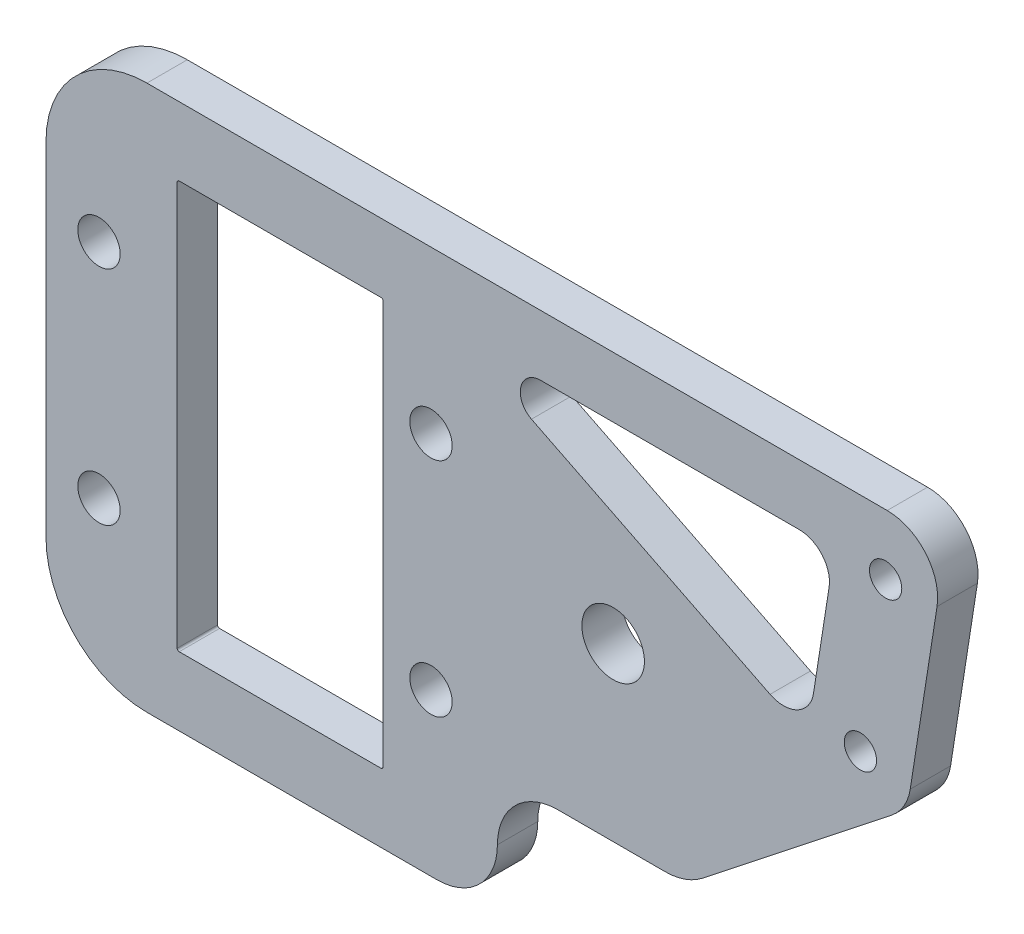
SolidWorks part; units mm, degrees
ref_plane "前视基准面" through (0, 0, 0) normal (0, 0, 1) x (1, 0, 0)
ref_plane "上视基准面" through (0, 0, 0) normal (0, 1, 0) x (1, 0, 0)
ref_plane "右视基准面" through (0, 0, 0) normal (1, 0, 0) x (0, 0, -1)
sketch "草图1" plane through (0, 0, 0) normal (0, 0, 1) x (1, 0, 0)
  line L0 (-10.2, 20.2) -> (10.2, 20.2)
  line L1 (-10, -20) -> (10, -20) construction
  line L2 (-10, -20) -> (-10, 20) construction
  line L3 (-10, 20) -> (10, 20) construction
  line L4 (10, -20) -> (10, 20) construction
  line L5 (-10, -20) -> (10, 20) construction
  line L6 (-10, 20) -> (10, -20) construction
  line L7 (10.2, -20.2) -> (10.2, 20.2)
  line L8 (-10.2, -20.2) -> (10.2, -20.2)
  line L9 (-10.2, -20.2) -> (-10.2, 20.2)
  line L10 (-13.2, 27) -> (60.1562, 27)
  line L11 (33, 25) -> (33, -25) construction
  line L12 (21.5311, -27) -> (-13.2, -27)
  line L13 (-23.2, -17) -> (-23.2, 17)
  line L15 (27.7237, -24.8519) -> (60.5963, 1.0741)
  line L16 (62.4401, 4.2281) -> (65.0963, 21.2281)
  circle A0 centre (33, 2) radius 3.1
  arc A1 (-13.2, -27) -> (-23.2, -17) centre (-13.2, -17) cw
  arc A2 (-13.2, 27) -> (-23.2, 17) centre (-13.2, 17) ccw
  circle A6 centre (33, 2) radius 12.5 construction
  circle A9 centre (60, 21) radius 1.6
  circle A10 centre (57.5, 5) radius 1.6
  arc A12 (60.5963, 1.0741) -> (62.4401, 4.2281) centre (57.5, 5) ccw
  arc A13 (21.5311, -27) -> (27.7237, -24.8519) centre (21.5311, -17) ccw
  arc A14 (65.0963, 21.2281) -> (60.1562, 27) centre (60.1562, 22) ccw
  point P0 (0, 0)
  point P32 (25, -27)
  dimension "D8" = 6.2
  dimension "D10" = 10
  dimension "D11" = 3.2
  dimension "D12" = 19
  dimension "D13" = 25
  dimension "D9" = 25
  dimension "D14" = 27
  dimension "D15" = 3.2
  dimension "D18" = 10
  dimension "D20" = 10
  dimension "D21" = 5
  dimension "D1" = 40
  dimension "D2" = 20
  dimension "D3" = 0.2
  dimension "D4" = 7
  dimension "D5" = 7
  dimension "D6" = 13
  dimension "D7" = 43
  dimension "D16" = 3
  dimension "D17" = 24.5
  dimension "D19" = 25
  dimension "D22" = 5
extrude "凸台-拉伸1" add sketch "草图1" along normal blind 4
fillet "圆角1" radius 0.2 4 edges at (10.2, -20.2, 2) (-10.2, -20.2, 2) (-10.2, 20.2, 2) (10.2, 20.2, 2)
sketch "草图2" plane through (0, 0, 4) normal (0, 0, 1) x (1, 0, 0)
  line L0 (14.95, 11) -> (14.95, -11) construction
  line L1 (9.95, 20.25) -> (9.95, -49979.75) construction
  line L2 (0, 0) -> (50000, 0) construction
  line L3 (10.2, -20) -> (10.2, 20) construction
  line L4 (0, 0.6321) -> (0, 50000.6321) construction
  line L5 (-17.95, 11) -> (-17.95, -11) construction
  circle A0 centre (14.95, 11) radius 2.1
  circle A4 centre (14.95, -11) radius 2.1
  circle A5 centre (-17.95, -11) radius 2.1
  circle A6 centre (-17.95, 11) radius 2.1
  dimension "D1" = 4.2
  dimension "D2" = 22
  dimension "D3" = 17.95
  dimension "D6" = 4.2
  dimension "D7" = 4.2
  dimension "D8" = 17.95
  dimension "D4" = 0.25
  dimension "D5" = 5
extrude "切除-拉伸1" cut sketch "草图2" against normal blind 4
sketch "草图3" plane through (0, 0, 4) normal (0, 0, 1) x (1, 0, 0)
  line L0 (25.798, 21) -> (51.4342, 21)
  line L1 (54.3982, 17.5369) -> (52.8522, 7.6426)
  line L2 (48.5495, 5.4209) -> (24.9056, 17.2102)
  line L3 (60.1562, 27) -> (-13.2, 27) construction
  line L4 (14.95, 11) -> (33, 2) construction
  line L5 (57.5, 5) -> (60, 21) construction
  line L6 (62.4401, 4.2281) -> (65.0963, 21.2281) construction
  arc A0 (54.3982, 17.5369) -> (51.4342, 21) centre (51.4342, 18) ccw
  arc A1 (24.9056, 17.2102) -> (25.798, 21) centre (25.798, 19) cw
  arc A2 (48.5495, 5.4209) -> (52.8522, 7.6426) centre (49.8882, 8.1057) ccw
  dimension "3" = 3
  dimension "D2" = 2
  dimension "D3" = 3
  dimension "D1" = 6
  dimension "D4" = 10
  dimension "D5" = 10
extrude "切除-拉伸2" cut sketch "草图3" against normal blind 10
sketch "草图4" plane through (0, 0, 4) normal (0, 0, 1) x (1, 0, 0)
  line L1 (21.5311, -27) -> (66.3276, -27)
  line L2 (21.5311, -27) -> (21.5311, -15)
  line L3 (21.5311, -15) -> (66.3276, -15)
  line L4 (66.3276, -27) -> (66.3276, -15)
  dimension "D1" = 12
extrude "切除-拉伸3" cut sketch "草图4" against normal blind 10
fillet "圆角2" radius 6 3 edges at (40.2153, -15, 2) (21.5311, -27, 2) (21.5311, -15, 2)
equation "\"4。2\"=3.2"
equation "\"6。2\"=6.5866"
equation "\"3。2\"=6.2"
equation "\"12。5\"=10"
